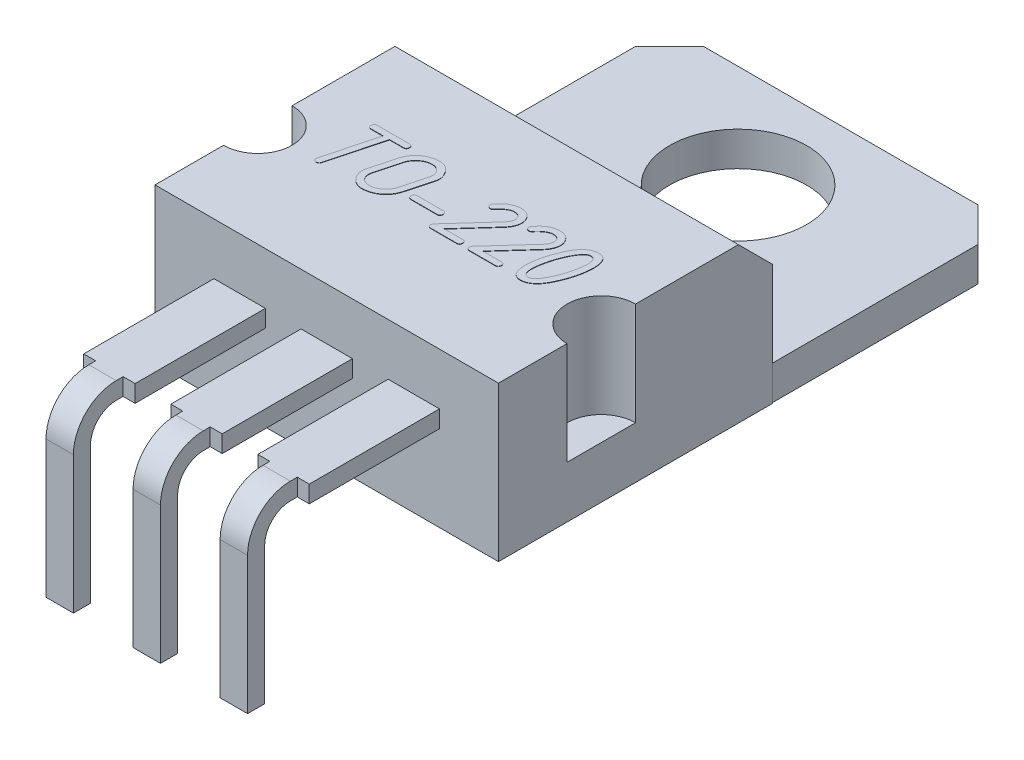
SolidWorks part; units mm, degrees
ref_plane "Front" through (0, 0, 0) normal (0, 0, 1) x (1, 0, 0)
ref_plane "Top" through (0, 0, 0) normal (0, 1, 0) x (1, 0, 0)
ref_plane "Right" through (0, 0, 0) normal (1, 0, 0) x (0, 0, -1)
sketch "Эскиз1" plane through (0, 0, 0) normal (0, 1, 0) x (1, 0, 0)
  line L0 (0, 0) -> (8, 0)
  line L1 (8, 0) -> (8, 6)
  line L2 (8, 6) -> (9, 6)
  line L3 (9, 6) -> (9, 12)
  line L4 (8, 13) -> (0, 13)
  line L5 (-1, 12) -> (-1, 6)
  line L6 (-1, 6) -> (0, 6)
  line L7 (0, 6) -> (0, 0)
  line L8 (0, 13) -> (-1, 12)
  line L9 (9, 12) -> (8, 13)
  line L10 (-1, 9) -> (9, 9) construction
  line L11 (4, 13) -> (4, 0) construction
  circle A0 centre (4, 10) radius 2
  point P6 (9, 13)
  point P7 (-1, 13)
  dimension "D6" = 4
  dimension "D10" = 5
  dimension "D1" = 10
  dimension "D2" = 8
  dimension "D3" = 6
  dimension "D4" = 1
  dimension "D5" = 7
  dimension "D7" = 3
extrude "Бобышка-Вытянуть1" add sketch "Эскиз1" along normal blind 1
sketch "Эскиз2" plane through (0, 1, 0) normal (0, 1, 0) x (1, 0, 0)
  line L0 (0, 6) -> (0, 0) construction
  line L1 (-1.01, 6) -> (9.01, 6)
  line L2 (-1.01, 6) -> (-1.01, -2)
  line L3 (-1.01, -2) -> (9.01, -2)
  line L4 (9.01, 6) -> (9.01, -2)
  line L5 (8, 0) -> (8, 6) construction
  line L7 (0, 6) -> (8, 6)
  line L8 (0, 6) -> (0, 0)
  line L9 (0, 0) -> (8, 0)
  line L10 (8, 6) -> (8, 0)
  line M1 (0, 6) -> (0, 0)
  line M2 (0, 0) -> (8, 0)
  line M3 (8, 0) -> (8, 6)
  line M4 (8, 6) -> (9, 6)
  line M10 (-1, 6) -> (0, 6)
  dimension "D1" = 1.01
  dimension "D2" = 1.01
  dimension "D3" = 8
extrude "Бобышка-Вытянуть3" add sketch "Эскиз2" against normal blind 1.01 contours L4 L2 L3 M4 M3 M2 M1 M10 region at (-1.005, 1, -5.8718)
extrude "Бобышка-Вытянуть4" add sketch "Эскиз2<5>" along normal blind 3.5 contours L1 M1 M2 M3 | L4 L2 L3 M4 M3 M2 M1 M10 region at (-1.005, 1, -5.8718) region at (4, 1, -3)
sketch "Эскиз2<5>" plane through (0, 1, 0) normal (0, 1, 0) x (1, 0, 0) same geometry as "Эскиз2"
sketch "Эскиз3" plane through (0, 0, 2) normal (0, 0, 1) x (1, 0, 0)
  line L0 (4, 4.5) -> (4, -0.01) construction
  line L1 (3.25, 2.99) -> (4.75, 2.99)
  line L2 (3.25, 2.99) -> (3.25, 2.49)
  line L3 (3.25, 2.49) -> (4.75, 2.49)
  line L4 (4.75, 2.99) -> (4.75, 2.49)
  line L5 (-1.01, 4.5) -> (9.01, 4.5) construction
  line L6 (-1.01, -0.01) -> (9.01, -0.01) construction
  dimension "D1" = 0.5
  dimension "D2" = 1.5
  dimension "D3" = 0.75
  dimension "D4" = 2.5
ref_plane "Плоскость1" through (4, 0, 0) normal (-1, 0, 0) x (0, 0, 1)
extrude "Бобышка-Вытянуть5" add sketch "Эскиз3" along normal blind 3.8
sketch "Эскиз4" plane through (0, 0, 5.8) normal (0, 0, 1) x (1, 0, 0)
  line L0 (4.75, 2.99) -> (3.25, 2.99) construction
  line L1 (3.6, 2.99) -> (4.4, 2.99)
  line L2 (3.6, 2.99) -> (3.6, 2.49)
  line L3 (3.6, 2.49) -> (4.4, 2.49)
  line L4 (4.4, 2.99) -> (4.4, 2.49)
  line L5 (3.25, 2.49) -> (4.75, 2.49) construction
  line L6 (4, 2.99) -> (4, 2.49) construction
  line L7 (4, 2.4805) -> (4, -2.4805) construction
  dimension "D1" = 0.8
  dimension "D2" = 0.4
sketch "Эскиз7" plane through (4, 0, 0) normal (-1, 0, 0) x (0, 0, 1)
  line L0 (5.8, 2.74) -> (6, 2.74)
  line L1 (5.8, 2.99) -> (5.8, 2.49) construction
  line L2 (7, 1.74) -> (7, -2.26)
  arc A0 (7, 1.74) -> (6, 2.74) centre (6, 1.74) ccw
  point P7 (7, 2.74)
  dimension "D3" = 1
  dimension "D1" = 1.2
  dimension "D2" = 5
sweep "По траектории1" add profiles "Эскиз4" path "Эскиз7"
pattern_linear "Линейный массив1" count 2 spacing 2.54 along (-1, 0, 0) count 2 spacing 2.54 along (1, 0, 0) of "Бобышка-Вытянуть5", "По траектории1"
sketch "Эскиз8" plane through (0, 4.5, 0) normal (0, 1, 0) x (1, 0, 0)
  line L0 (0, 0.9176) -> (7.5218, 0.9176) construction
  text T0 "TO-220" font "ISOCPEUR" height in points 8
extrude "Бобышка-Вытянуть6" add sketch "Эскиз8" along normal blind 0.01
chamfer "Фаска1" distance 1 angle 45 1 edges at (4, 4.5, -6)
sketch "Эскиз9" plane through (0, 4.5, 0) normal (0, 1, 0) x (1, 0, 0)
  line L0 (-1.01, 5) -> (-1.01, -2) construction
  line L1 (9.01, 5) -> (9.01, -2) construction
  line L2 (-1.01, -2) -> (9.01, -2) construction
  circle A0 centre (-1.01, 1) radius 1
  circle A1 centre (9.01, 1) radius 1
  dimension "D1" = 2
  dimension "D2" = 3
  dimension "D3" = 3
  dimension "D4" = 2
extrude "Вырез-Вытянуть1" cut sketch "Эскиз9" against normal blind 3
